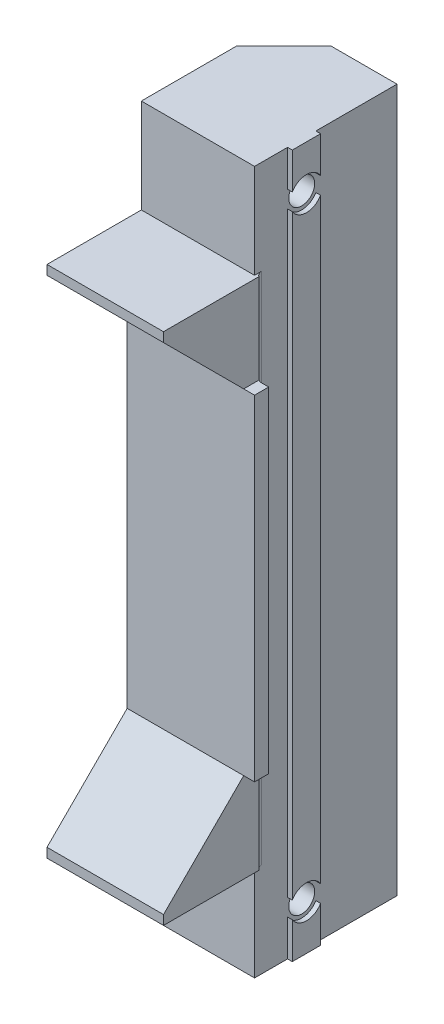
SolidWorks part; units mm, degrees
ref_plane "Top Plane" through (0, 0, 0) normal (0, 0, 1) x (1, 0, 0)
ref_plane "Right Plane" through (0, 0, 0) normal (0, 1, 0) x (1, 0, 0)
ref_plane "Front Plane" through (0, 0, 0) normal (1, 0, 0) x (0, 0, -1)
sketch "Sketch1" plane through (0, 0, 0) normal (0, 0, 1) x (1, 0, 0)
  line L0 (74.75, 0) -> (-74.75, 0)
  line L1 (-74.75, 0) -> (74.75, 0) construction
  line L5 (-74.75, 0) -> (-74.75, 30)
  line L6 (-74.75, 30) -> (-88.75, 30)
  line L7 (-88.75, 30) -> (-88.75, -13)
  line L8 (-88.75, -13) -> (84.25, -13)
  line L10 (84.25, 17) -> (84.25, -13)
  line L11 (74.75, 17) -> (84.25, 17)
  line L12 (74.75, 0) -> (74.75, 17)
  dimension "D1" = 149.5
  dimension "D2" = 13
  dimension "D3" = 30
  dimension "D4" = 14
  dimension "D5" = 9.5
  dimension "D6" = 17
extrude "Boss-Extrude1" add sketch "Sketch1" along normal blind 7.2
sketch "Sketch2" plane through (0, -13, 0) normal (0, -1, 0) x (1, 0, 0)
  line L1 (-88.75, 0) -> (84.25, 0) construction
  line L2 (-56.25, 4.5) -> (37.75, 4.5) construction
  circle A0 centre (-56.25, 4.5) radius 1.1
  circle A1 centre (37.75, 4.5) radius 1.1
  dimension "D2" = 2.2
  dimension "D1" = 4.5
  dimension "D3" = 94
  dimension "D4" = 18.5
extrude "Cut-Extrude1" cut sketch "Sketch2" against normal through all
sketch "Sketch3" plane through (0, -13, 0) normal (0, -1, 0) x (1, 0, 0)
  circle A0 centre (-56.25, 4.5) radius 2.25
  circle A1 centre (37.75, 4.5) radius 2.25
  dimension "D1" = 4.5
extrude "Cut-Extrude2" cut sketch "Sketch3" against normal offset from surface (5.5 mm away) 7.5 up to face at (-55.15, 0, 4.5)
sketch "Sketch4" plane through (0, 0, 7.2) normal (0, 0, 1) x (1, 0, 0)
  line L0 (84.25, -13) -> (84.25, 17) construction
  line L1 (-88.75, -13) -> (84.25, -13)
  line L2 (-88.75, -13) -> (-88.75, 30)
  line L4 (84.25, -13) -> (84.25, 2.9894)
  line L5 (74.75, 17) -> (74.75, 0) construction
  line L6 (-88.75, 30) -> (-88.75, -13) construction
  line L7 (74.75, 6) -> (74.75, 17)
  line L8 (74.75, 17) -> (84.25, 17)
  line L9 (84.25, 17) -> (84.25, 2.9894)
  line L10 (-88.75, 30) -> (-74.75, 30)
  line L12 (-74.75, 0) -> (-74.75, 30) construction
  line L13 (-74.75, 30) -> (-74.75, 6)
  line L14 (-74.75, 6) -> (74.75, 6)
  point P7 (74.75, 6)
  dimension "D1" = 6
extrude "Boss-Extrude2" add sketch "Sketch4" along normal blind 3
fillet "Fillet1" radius 11 2 edges at (74.75, 6, 8.7) (-74.75, 6, 8.7)
sketch "Sketch5" plane through (0, -13, 0) normal (0, -1, 0) x (1, 0, 0)
  line L0 (-74.75, 30.2) -> (-71.75, 30.2)
  line L1 (-88.75, 10.2) -> (-74.75, 10.2)
  line L2 (-88.75, 10.2) -> (-88.75, 33.2)
  line L4 (-74.75, 10.2) -> (-74.75, 17.2)
  line L5 (-71.75, 30.2) -> (-71.75, 33.2)
  line L6 (-71.75, 33.2) -> (-88.75, 33.2)
  line L7 (-74.75, 23.2) -> (-74.75, 30.2)
  line L8 (-74.75, 17.2) -> (-73.75, 17.2)
  line L10 (-74.75, 23.2) -> (-73.75, 23.2)
  line L11 (-73.75, 17.2) -> (-73.75, 23.2)
  dimension "D1" = 20
  dimension "D2" = 3
  dimension "D3" = 6
  dimension "D4" = 1
extrude "Boss-Extrude3" add sketch "Sketch5" against normal up to surface (43 mm away) up to face at (-81.75, 30, 5.1)
sketch "Sketch6" plane through (0, -13, 0) normal (0, -1, 0) x (1, 0, 0)
  line L21 (74.75, 10.2) -> (74.75, 17.2)
  line L22 (73.75, 17.2) -> (73.75, 23.2)
  line L23 (71.75, 30.2) -> (71.75, 33.2)
  line L24 (71.75, 33.2) -> (84.25, 33.2)
  line L25 (74.75, 30.2) -> (71.75, 30.2)
  line L26 (74.75, 23.2) -> (74.75, 30.2)
  line L27 (73.75, 23.2) -> (74.75, 23.2)
  line L28 (74.75, 17.2) -> (73.75, 17.2)
  line L29 (84.25, 33.2) -> (84.25, 10.2)
  line L30 (74.75, 10.2) -> (84.25, 10.2)
  dimension "D1" = 6
  dimension "D2" = 1
  dimension "D3" = 20
  dimension "D4" = 3
extrude "Boss-Extrude4" add sketch "Sketch6" against normal up to surface (30 mm away) up to face at (78.55, 17, 5.52)
fillet "Fillet2" radius 1.5 4 edges at (-74.75, 8.5, 30.2) (-74.75, 2, 10.2) (74.75, 2, 30.2) (74.75, 2, 10.2)
sketch "Sketch7" plane through (84.25, 0, 0) normal (1, 0, 0) x (0, 0, -1)
  line L0 (-10.2, -13) -> (-10.2, 6) construction
  line L1 (-33.2, -13) -> (0, -13) construction
  line L2 (-20.2, -3.5) -> (-10.2, -3.5) construction
  circle A0 centre (-20.2, -3.5) radius 2.75
  dimension "D1" = 5.5
  dimension "D2" = 10
extrude "Cut-Extrude3" cut sketch "Sketch7" against normal through all
sketch "Sketch8" plane through (84.25, 0, 0) normal (1, 0, 0) x (0, 0, -1)
  circle A0 centre (-20.2, -3.5) radius 5.25
  dimension "D1" = 10.5
extrude "Cut-Extrude4" cut sketch "Sketch8" against normal offset from surface (5 mm away) 4.5 up to face at (74.75, 2, 25.95)
sketch "Sketch10" plane through (-88.75, 0, 0) normal (-1, 0, 0) x (0, 0, 1)
  circle A0 centre (20.2, -3.5) radius 5.25
  circle A1 centre (20.2, -3.5) radius 5.25 construction
extrude "Cut-Extrude6" cut sketch "Sketch10" against normal offset from surface (2.5 mm away) 11.5 up to face at (-74.75, 8.5, 25.95)
chamfer "Chamfer1" distance 2.5 angle 45 2 edges at (79.25, -6.25, 20.2) (-86.25, -0.75, 20.2)
sketch "Sketch9" plane through (73.75, 0, 0) normal (-1, 0, 0) x (0, 0, 1)
  circle A0 centre (20.2, -3.5) radius 3.5
  dimension "D1" = 7
extrude "Cut-Extrude5" cut sketch "Sketch9" against normal up to surface and the other way up to surface up to face at (74.75, 2, 25.95) other way up to face at (-74.75, 8.5, 25.95)
mirror "Mirror1" about plane through (-88.75, -13, 7.2) normal (0, 1, 0) of bodies 111 104
delete or keep bodies "Body-Delete/Keep 1" type delete bodies bodies 111
sketch "Sketch11" plane through (0, -13, 0) normal (0, 1, 0) x (1, 0, 0)
  line L0 (71.75, -33.2) -> (71.75, -17.2)
  line L1 (84.25, 0) -> (71.75, 0)
  line L2 (84.25, 0) -> (84.25, -33.2)
  line L3 (84.25, -33.2) -> (71.75, -33.2)
  line L5 (71.75, 0) -> (-74.75, 0)
  line L7 (71.75, -17.2) -> (-74.75, -17.2)
  line L8 (-74.75, 0) -> (-74.75, -17.2)
extrude "Cut-Extrude7" cut sketch "Sketch11" against normal through all
sketch "Sketch13" plane through (0, -13, 0) normal (0, 1, 0) x (1, 0, 0)
  line L0 (-88.75, -33.2) -> (-88.75, 0) construction
  line L1 (-88.75, -30.2) -> (-74.75, -30.2)
  line L2 (-88.75, -30.2) -> (-88.75, -33.2)
  line L3 (-88.75, -33.2) -> (-71.75, -33.2)
  line L4 (-71.75, -30.2) -> (-71.75, -33.2)
  line L5 (-73.25, -30.2) -> (-71.75, -30.2) construction
  line L8 (-71.75, -30.2) -> (-71.75, -28.7)
  line L9 (-71.75, -28.7) -> (-74.75, -28.7)
  line L10 (-74.75, -30.2) -> (-74.75, -28.7)
extrude "Cut-Extrude8" cut sketch "Sketch13" against normal blind 20
sketch "Sketch14" plane through (-88.75, 0, 0) normal (-1, 0, 0) x (0, 0, 1)
  line L0 (33.2, -33) -> (50.2, -33)
  line L2 (33.2, -56) -> (33.2, -33) construction
  line L3 (33.2, -50) -> (33.2, -33)
  line L4 (33.2, -50) -> (35.2, -50) construction
  line L5 (35.2, -50) -> (50.2, -35)
  line L6 (50.2, -35) -> (50.2, -33)
  line L7 (35.2, -50) -> (33.2, -52)
  line L8 (33.2, -52) -> (33.2, -50)
  dimension "D1" = 20
  dimension "D2" = 2
extrude "Boss-Extrude6" add sketch "Sketch14" against normal up to surface (17 mm away) up to face at (-71.75, -44.5, 31.7)
sketch "Sketch15" plane through (-88.75, 0, 0) normal (-1, 0, 0) x (0, 0, 1)
  line L0 (33.2, -52) -> (0, -52)
  line L1 (0, -56) -> (0, -13) construction
  line L2 (0, -52) -> (0, -13)
  line L3 (0, -13) -> (30.2, -13)
  line L4 (30.2, -33) -> (30.2, -13) construction
  line L5 (30.2, -13) -> (0, -13) construction
  line L6 (30.2, -13) -> (30.2, -33)
  line L7 (30.2, -33) -> (50.2, -33)
  line L8 (50.2, -33) -> (50.2, -35)
  line L9 (50.2, -35) -> (33.2, -52)
  circle A0 centre (20.2, -22.5) radius 5.25
  circle A1 centre (20.2, -22.5) radius 5.25 construction
extrude "Boss-Extrude7" add sketch "Sketch15" along normal blind 10
chamfer "Chamfer3" distance 10 angle 45 1 edges at (-98.75, -32.5, 0)
sketch "Sketch12" plane through (0, -56, 0) normal (0, -1, 0) x (1, 0, 0)
  line L10 (-88.75, 0) -> (-74.75, 0)
  line L11 (-74.75, 0) -> (-74.75, 17.2)
  line L12 (-74.75, 17.2) -> (-73.75, 17.2)
  line L13 (-73.75, 17.2) -> (-73.75, 23.2)
  line L14 (-73.75, 23.2) -> (-74.75, 23.2)
  line L15 (-74.75, 23.2) -> (-74.75, 28.7)
  line L16 (-73.25, 30.2) -> (-71.75, 30.2)
  line L17 (-71.75, 30.2) -> (-71.75, 33.2)
  line L18 (-71.75, 33.2) -> (-88.75, 33.2)
  line L19 (-88.75, 33.2) -> (-88.75, 0)
  line L20 (-88.75, 0) -> (-74.75, 0)
  line L21 (-74.75, 0) -> (-74.75, 17.2)
  line L22 (-74.75, 17.2) -> (-73.75, 17.2)
  line L23 (-73.75, 17.2) -> (-73.75, 23.2)
  line L24 (-73.75, 23.2) -> (-74.75, 23.2)
  line L25 (-74.75, 23.2) -> (-74.75, 28.7)
  line L26 (-73.25, 30.2) -> (-71.75, 30.2)
  line L27 (-71.75, 30.2) -> (-71.75, 33.2)
  line L28 (-71.75, 33.2) -> (-88.75, 33.2)
  line L30 (-88.75, 33.2) -> (-88.75, 0)
  arc A1 (-73.25, 30.2) -> (-74.75, 28.7) centre (-73.25, 28.7) ccw
  arc A2 (-73.25, 30.2) -> (-74.75, 28.7) centre (-73.25, 28.7) ccw
  dimension "D1" = 0
extrude "Boss-Extrude5" add sketch "Sketch12" against normal offset from surface (17.55 mm away) 5.45 up to face at (-80.5801, -33, 35.7444)
sketch "Sketch16" plane through (-71.75, 0, 0) normal (1, 0, 0) x (0, 0, -1)
  line L0 (-28.7, -52) -> (-33.2, -52)
  line L2 (-28.7, -52) -> (-28.7, -33)
  line L3 (-28.7, -33) -> (-30.2, -33)
  line L6 (-30.2, -56) -> (-30.2, -33)
  line L7 (-30.2, -33) -> (-50.2, -33)
  line L8 (-50.2, -33) -> (-50.2, -35)
  line L9 (-50.2, -35) -> (-33.2, -52)
  line L10 (-33.2, -52) -> (-33.2, -56)
  line L11 (-33.2, -56) -> (-30.2, -56)
  line L13 (-30.2, -33) -> (-50.2, -33)
  line L14 (-50.2, -33) -> (-50.2, -35)
  line L15 (-50.2, -35) -> (-33.2, -52)
  point P6 (0, 0)
  point P11 (-28.862, -52)
  line M8 (-30.2, -56) -> (-30.2, -33)
  line M9 (-30.2, -33) -> (-50.2, -33)
  line M10 (-50.2, -33) -> (-50.2, -35)
  line M11 (-50.2, -35) -> (-33.2, -52)
  dimension "D2" = 19
  dimension "D1" = 0
extrude "Cut-Extrude9" cut sketch "Sketch16" against normal offset from surface (2.3 mm away) 0.7 contours L0 M8 M9 M10 M11 | L2 L3 L0 M8 | L15 L14 L13 L3 L2 L0 region at (-71.75, -42.5, 29.45) region at (-71.75, -40.1479, 37.5411)
sketch "Sketch18" plane through (0, -52, 0) normal (0, -1, 0) x (1, 0, 0)
  line L4 (-98.75, 33.2) -> (-98.75, 10)
  line L5 (-98.75, 10) -> (-88.75, 0)
  line L6 (-88.75, 0) -> (-88.75, 33.2)
  line L7 (-88.75, 33.2) -> (-98.75, 33.2)
  line L8 (-98.75, 33.2) -> (-98.75, 10)
  line L9 (-98.75, 10) -> (-88.75, 0)
  line L10 (-88.75, 0) -> (-88.75, 33.2)
  line L11 (-88.75, 33.2) -> (-98.75, 33.2)
  dimension "D1" = 0
extrude "Boss-Extrude8" add sketch "Sketch18" along normal up to surface (4 mm away)
sketch "Sketch19" plane through (0, -56, 0) normal (0, -1, 0) x (1, 0, 0)
  line L11 (-88.75, 0) -> (-74.75, 0)
  line L12 (-74.75, 0) -> (-74.75, 17.2)
  line L13 (-74.75, 17.2) -> (-73.75, 17.2)
  line L14 (-73.75, 17.2) -> (-73.75, 23.2)
  line L15 (-73.75, 23.2) -> (-74.75, 23.2)
  line L16 (-74.75, 23.2) -> (-74.75, 28.7)
  line L17 (-73.25, 30.2) -> (-71.75, 30.2)
  line L18 (-71.75, 30.2) -> (-71.75, 33.2)
  line L19 (-71.75, 33.2) -> (-98.75, 33.2)
  line L20 (-98.75, 33.2) -> (-98.75, 10)
  line L21 (-98.75, 10) -> (-88.75, 0)
  line L22 (-88.75, 0) -> (-74.75, 0)
  line L23 (-74.75, 0) -> (-74.75, 17.2)
  line L24 (-74.75, 17.2) -> (-73.75, 17.2)
  line L25 (-73.75, 17.2) -> (-73.75, 23.2)
  line L26 (-73.75, 23.2) -> (-74.75, 23.2)
  line L27 (-74.75, 23.2) -> (-74.75, 28.7)
  line L28 (-73.25, 30.2) -> (-71.75, 30.2)
  line L29 (-71.75, 30.2) -> (-71.75, 33.2)
  line L30 (-71.75, 33.2) -> (-98.75, 33.2)
  line L31 (-98.75, 33.2) -> (-98.75, 10)
  line L32 (-98.75, 10) -> (-88.75, 0)
  arc A1 (-73.25, 30.2) -> (-74.75, 28.7) centre (-73.25, 28.7) ccw
  arc A2 (-73.25, 30.2) -> (-74.75, 28.7) centre (-73.25, 28.7) ccw
  dimension "D1" = 0
extrude "Boss-Extrude9" add sketch "Sketch19" along normal offset from surface (31.5 mm away) 54.5 up to face at (-82.5439, -33, 36.5932)
mirror "Mirror2" about plane through (0, -87.5, 0) normal (0, 1, 0) of bodies 121 119
